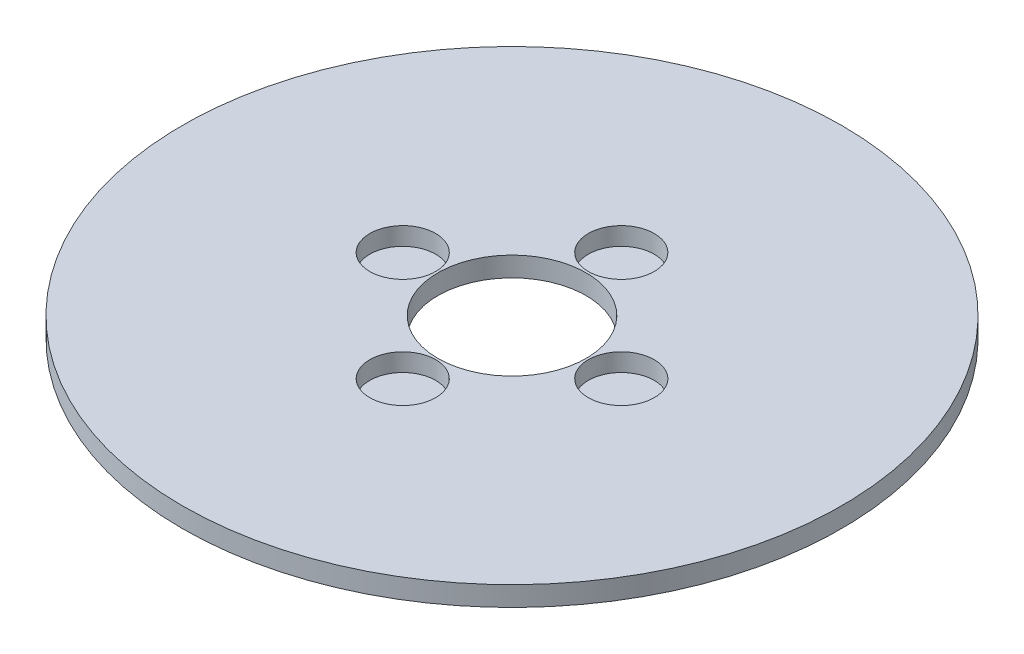
SolidWorks part; units mm, degrees
ref_plane "Front Plane" through (0, 0, 0) normal (0, 0, 1) x (1, 0, 0)
ref_plane "Top Plane" through (0, 0, 0) normal (0, 1, 0) x (1, 0, 0)
ref_plane "Right Plane" through (0, 0, 0) normal (1, 0, 0) x (0, 0, -1)
sketch "Sketch1" plane through (0, 0, 0) normal (0, 1, 0) x (1, 0, 0)
  circle A0 centre (0, 0) radius 100
  dimension "FLANGE_OD" = 200
extrude "Boss-Extrude1" add sketch "Sketch1" along normal blind 6
sketch "Sketch2" plane through (0, 0, 0) normal (0, 1, 0) x (1, 0, 0)
  circle A0 centre (0, 0) radius 22.5
  dimension "BORE_D" = 45
extrude "Cut-Extrude1" cut sketch "Sketch2" along normal through all
sketch "Sketch3" plane through (0, 6, 0) normal (0, 1, 0) x (1, 0, 0)
  circle A0 centre (0, 0) radius 33.1572 construction
  circle A1 centre (-33.1572, 0) radius 10
  dimension "BOLT_D" = 20
  dimension "BOLT_PCD" = 66.3144
extrude "Cut-Extrude2" cut sketch "Sketch3" against normal blind 5.4523
pattern_circular "CirPattern1" count 4 over 360 about axis through (0, 0, 0) along (0, 1, 0) of "Cut-Extrude2"
